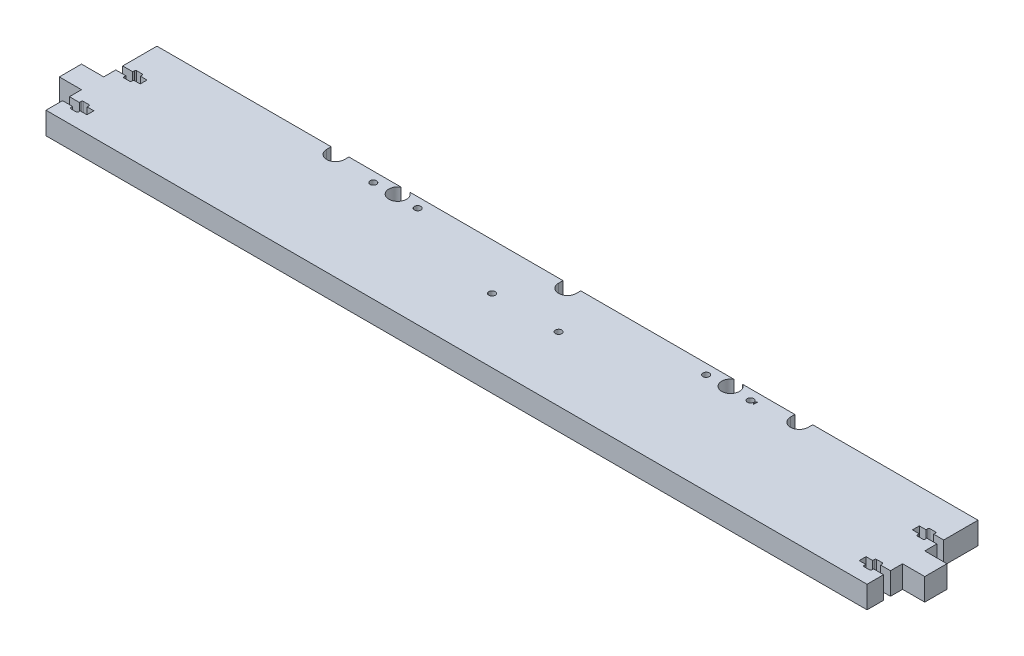
SolidWorks part; units mm, degrees
ref_plane "Front Plane" through (0, 0, 0) normal (0, 0, 1) x (1, 0, 0)
ref_plane "Top Plane" through (0, 0, 0) normal (0, 1, 0) x (1, 0, 0)
ref_plane "Right Plane" through (0, 0, 0) normal (1, 0, 0) x (0, 0, -1)
sketch "Sketch1" plane through (0, 0, 0) normal (0, 1, 0) x (1, 0, 0)
  line L0 (0, 25) -> (0, -25)
  line L1 (-185, 25) -> (0, 25)
  line L2 (-185, 25) -> (-185, -25) construction
  line L3 (-185, -25) -> (0, -25)
  line L4 (-185, -4) -> (-195, -4) construction
  line L5 (-185, 25) -> (0, 0) construction
  line L6 (-185, -25) -> (0, 0) construction
  line L7 (-185, -9) -> (-195, -9)
  line L8 (-195, -9) -> (-195, 1)
  line L9 (-195, 1) -> (-185, 1)
  line L10 (-185, 1) -> (-185, 25)
  line L11 (-185, -9) -> (-185, -25)
  line L47 (0, -25) -> (0, 25) construction
  line L89 (0, -25) -> (0, 25) construction
  point P0 (0, 0)
  dimension "D1" = 185
  dimension "D25" = 25
  dimension "D4" = 50
  dimension "D3" = 21
  dimension "D5" = 10
  dimension "D6" = 10
  dimension "D7" = 5
extrude "MainBody" add sketch "Sketch1" along normal blind 10 contours L3 region at (-93.5428, 0, 0.0428)
sketch "Sketch5" plane through (0, 10, 0) normal (0, 1, 0) x (1, 0, 0)
  line L0 (-185, 8) -> (-174, 8) construction
  line L1 (-185, 1) -> (-185, 25) construction
  line L2 (-185, 9.55) -> (-174, 9.55) construction
  line L3 (-174, 9.55) -> (-174, 6.45) construction
  line L4 (-174, 6.45) -> (-185, 6.45) construction
  line L5 (-185, 9.55) -> (-180.5, 9.55)
  line L6 (-180.5, 9.55) -> (-180.5, 10.35)
  line L7 (-180, 10.85) -> (-177.5, 10.85)
  line L8 (-177, 10.35) -> (-177, 9.55)
  line L9 (-177, 9.55) -> (-174, 9.55)
  line L10 (-174, 9.55) -> (-174, 6.45)
  line L11 (-185, 6.45) -> (-185, 9.55)
  line L12 (-195, -9) -> (-195, 1) construction
  line L13 (-185, 6.45) -> (-174, 6.45) construction
  line L14 (-177, 6.45) -> (-174, 6.45)
  line L15 (-177, 5.65) -> (-177, 6.45)
  line L16 (-180, 5.15) -> (-177.5, 5.15)
  line L17 (-180.5, 6.45) -> (-180.5, 5.65)
  line L18 (-185, 6.45) -> (-180.5, 6.45)
  line L19 (-185, 1) -> (-185, -9) construction
  line L20 (-195, -4) -> (-185, -4) construction
  line L21 (-195, -9) -> (-195, 1) construction
  line L22 (-185, -14.45) -> (-174, -14.45) construction
  line L23 (-174, -14.45) -> (-185, -14.45) construction
  line L24 (-174, -17.55) -> (-174, -14.45) construction
  line L25 (-185, -17.55) -> (-174, -17.55) construction
  line L26 (-185, -16) -> (-174, -16) construction
  line L27 (-185, -14.45) -> (-180.5, -14.45)
  line L28 (-180.5, -14.45) -> (-180.5, -13.65)
  line L29 (-180, -13.15) -> (-177.5, -13.15)
  line L30 (-177, -13.65) -> (-177, -14.45)
  line L31 (-177, -14.45) -> (-174, -14.45)
  line L32 (-185, -14.45) -> (-185, -17.55)
  line L33 (-174, -17.55) -> (-174, -14.45)
  line L34 (-177, -17.55) -> (-174, -17.55)
  line L35 (-177, -18.35) -> (-177, -17.55)
  line L36 (-180, -18.85) -> (-177.5, -18.85)
  line L37 (-180.5, -17.55) -> (-180.5, -18.35)
  line L38 (-185, -17.55) -> (-180.5, -17.55)
  line L39 (-185, 6.45) -> (-174, 6.45) construction
  arc A0 (-177.5, 10.85) -> (-177, 10.35) centre (-177.5, 10.35) cw
  arc A1 (-180.5, 10.35) -> (-180, 10.85) centre (-180, 10.35) cw
  arc A2 (-180.5, 5.65) -> (-180, 5.15) centre (-180, 5.65) ccw
  arc A3 (-177.5, 5.15) -> (-177, 5.65) centre (-177.5, 5.65) ccw
  arc A4 (-177.5, -13.15) -> (-177, -13.65) centre (-177.5, -13.65) cw
  arc A5 (-180.5, -13.65) -> (-180, -13.15) centre (-180, -13.65) cw
  arc A6 (-180.5, -18.35) -> (-180, -18.85) centre (-180, -18.35) ccw
  arc A7 (-177.5, -18.85) -> (-177, -18.35) centre (-177.5, -18.35) ccw
  point P6 (-195, -4)
  point P17 (-177, 10.85)
  point P20 (-180.5, 10.85)
  point P29 (-180.5, 5.15)
  point P30 (-177, 5.15)
  point P61 (-177, -13.15)
  point P62 (-180.5, -13.15)
  point P63 (-180.5, -18.85)
  point P64 (-177, -18.85)
  dimension "D8" = 0.5
  dimension "D1" = 11
  dimension "D2" = 1.55
  dimension "D4" = 3.5
  dimension "D5" = 8
  dimension "D6" = 2.85
  dimension "D7" = 12
extrude "ScrewCutouts" cut sketch "Sketch5" against normal through all
mirror "Mirror1" about plane through (0, 0, 0) normal (1, 0, 0) of "ScrewCutouts", "MainBody"
sketch "Sketch3" plane through (0, 10, 0) normal (0, 1, 0) x (1, 0, 0)
  line L0 (2, 25) -> (2, -25) construction
  line L1 (-185, 25) -> (185, 25) construction
  line L2 (-185, -25) -> (185, -25) construction
  line L3 (-63, 20.5) -> (-83, 20.5) construction
  line L4 (-73, 17.5) -> (-73, 25.5) construction
  line L5 (77, 17.5) -> (77, 25.5) construction
  line L6 (67, 20.5) -> (87, 20.5) construction
  circle A0 centre (-73, 21.5) radius 4
  circle A1 centre (-83, 20.5) radius 1.45
  circle A2 centre (-63, 20.5) radius 1.45
  circle A3 centre (67, 20.5) radius 1.45
  circle A4 centre (87, 20.5) radius 1.45
  circle A5 centre (77, 21.5) radius 4
  dimension "D2" = 8
  dimension "D4" = 2.9
  dimension "D1" = 3.5
  dimension "D5" = 75
  dimension "D6" = 2
  dimension "D3" = 10
  dimension "D7" = 1
extrude "RodCutouts" cut sketch "Sketch3" against normal through all
sketch "Sketch6" plane through (0, 10, 0) normal (0, 1, 0) x (1, 0, 0)
  line L0 (-73, 21.5) -> (77, 21.5) construction
  line L1 (2, 21.5) -> (2, -25) construction
  line L2 (-185, -25) -> (185, -25) construction
  line L3 (17, 4) -> (-13, 4) construction
  line L4 (-71.0635, 25) -> (75.0635, 25) construction
  circle A0 centre (-13, 4) radius 1.45
  circle A1 centre (17, 4) radius 1.45
  point P13 (2, 4)
  dimension "D3" = 21
  dimension "D1" = 2.9
  dimension "D2" = 15
extrude "Cut-Extrude1" cut sketch "Sketch6" against normal through all
sketch "Sketch7" plane through (0, 10, 0) normal (0, 1, 0) x (1, 0, 0)
  line L0 (-73, 21.5) -> (77, 21.5) construction
  line L1 (2, 21.5) -> (2, -25) construction
  line L3 (-102.5, 25) -> (-102.5, 23) construction
  line L4 (-185, 25) -> (-74.9365, 25) construction
  line L5 (-98.5, 25) -> (-98.5, 23)
  line L6 (-106.5, 25) -> (-106.5, 23)
  line L7 (106.5, 25) -> (106.5, 23) construction
  line L8 (102.5, 25) -> (102.5, 23)
  line L9 (110.5, 25) -> (110.5, 23)
  line L12 (-185, -25) -> (185, -25) construction
  arc A0 (-98.5, 25) -> (-106.5, 25) centre (-102.5, 25) ccw
  arc A1 (-106.5, 23) -> (-98.5, 23) centre (-102.5, 23) ccw
  arc A2 (102.5, 25) -> (110.5, 25) centre (106.5, 25) cw
  arc A3 (110.5, 23) -> (102.5, 23) centre (106.5, 23) cw
  point P12 (-102.5, 24)
  point P19 (106.5, 24)
  dimension "D1" = 4
  dimension "D2" = 2
  dimension "D3" = 104.5
extrude "BedAdjustmentScrewCutout" cut sketch "Sketch7" against normal through all
sketch "Sketch8" plane through (0, 10, 0) normal (0, 1, 0) x (1, 0, 0)
  line L0 (88.25, 20.5) -> (89.25, 20.5) construction
  line L1 (88.45, 20.5) -> (88.45, 25) construction
  line L2 (88.25, 20.5) -> (89.25, 21.5)
  line L3 (89.25, 21.5) -> (89.25, 19.5)
  line L4 (88.25, 20.5) -> (89.25, 19.5)
  line L5 (78.9365, 25) -> (102.5, 25) construction
  circle A1 centre (87, 20.5) radius 1.45 construction
  point P9 (89.25, 20.5)
  dimension "D1" = 1
  dimension "D2" = 1
  dimension "D3" = 0.2
extrude "DirectionKey" cut sketch "Sketch8" against normal through all
sketch "Sketch9" plane through (0, 10, 0) normal (0, 1, 0) x (1, 0, 0)
  line L0 (-13, 4) -> (17, 4) construction
  line L1 (2, 4) -> (2, 25) construction
  line L2 (-71.0635, 25) -> (75.0635, 25) construction
  line L3 (2, 27) -> (2, 23) construction
  line L4 (6, 27) -> (6, 23)
  line L5 (-2, 27) -> (-2, 23)
  arc A0 (6, 27) -> (-2, 27) centre (2, 27) ccw
  arc A1 (-2, 23) -> (6, 23) centre (2, 23) ccw
  point P10 (2, 25)
  dimension "D1" = 4
  dimension "D2" = 2
extrude "Cut-Extrude2" cut sketch "Sketch9" against normal through all
equation "\"Y-ROD-SPACING\"=75"
equation "\"Y-BED-OFFSET\"=2"
equation "\"T-SLOT-NUT-FILLET-RADIUS\"=0.5"
equation "\"T-SLOT-SCREW-SHAFT-RADIUS\"=1.55"
equation "\"T-SLOT-SCREW-SHAFT-CUTOUT-LENGTH\"=11"
equation "\"T-SLOT-NUT-DEPTH\"=3.5"
equation "\"T-SLOT-NUT-WIDTH\"=2.85"
equation "\"T-SLOT-NUT-END-DISTANCE\"=8"
equation "\"ACRYLIC-TAB-CUTOUT-SIZE\"=\"ACRYLIC-THICKNESS\"+\"ACRYLIC-TAB-TOLERANCE\"*2"
equation "\"ACRYLIC-M3-HOLE\"=2.9"
equation "\"D1@Sketch5\"=\"T-SLOT-SCREW-SHAFT-CUTOUT-LENGTH\""
equation "\"D2@Sketch5\"=\"T-SLOT-SCREW-SHAFT-RADIUS\""
equation "\"D4@Sketch5\"=\"T-SLOT-NUT-DEPTH\""
equation "\"D5@Sketch5\"=\"T-SLOT-NUT-END-DISTANCE\""
equation "\"D6@Sketch5\"=\"T-SLOT-NUT-WIDTH\""
equation "\"D8@Sketch5\"=\"T-SLOT-NUT-FILLET-RADIUS\""
equation "\"D4@Sketch3\"=\"ACRYLIC-M3-HOLE\""
equation "\"D5@Sketch3\"=\"Y-ROD-SPACING\""
equation "\"D6@Sketch3\"=\"Y-BED-OFFSET\""
equation "\"Y-BED-ROD-INSET\"=3.5"
equation "\"D1@Sketch3\"=\"Y-BED-ROD-INSET\""
equation "\"SMOOTHROD-CAP-SCREW-DISTANCE\"=20"
equation "\"D3@Sketch3\"=\"SMOOTHROD-CAP-SCREW-DISTANCE\"/2"
equation "\"ACRYLIC-TAB-WIDTH\"=\"ACRYLIC-THICKNESS\""
equation "\"FRAME-WIDTH-INNER\"=370"
equation "\"D6@Sketch1\"=\"ACRYLIC-TAB-WIDTH\""
equation "\"D5@Sketch1\"=\"ACRYLIC-TAB-WIDTH\""
equation "\"D1@Sketch1\"=\"FRAME-WIDTH-INNER\"/2"
equation "\"X-ROD-SPACING\"=45"
equation "\"Z-ROD-SPACING\"=17.5"
equation "\"ACRYLIC-THICKNESS\"=10"
equation "\"ACRYLIC-THICKNESS2\"=4.5"
equation "\"NEMA17-HOLE-SPACING\"=31"
equation "\"NEMA17-CENTRAL-CUTOUT\"=22.5"
equation "\"Z-BRACKET-REACH\"=55"
equation "\"TOP-BRACKET-SPACING\"=40"
equation "\"SMOOTHROD-X-LENGTH\"=350"
equation "\"SMOOTHROD-Y-LENGTH\"=350"
equation "\"SMOOTHROD-Z-LENGTH\"=350"
equation "\"SMOOTHROD-TIGHTENING-HEADROOM\"=.25"
equation "\"LEADSCREW-Z-LENGTH\"=300"
equation "\"SCREW-LENGTH-FRAME\"=\"ACRYLIC-THICKNESS\" + 10"
equation "\"SCREW-HEAD-RADIUS\"=6"
equation "\"PRINTED-X-SMOOTHROD-DIAMETER\"=9.0"
equation "\"PRINTED-X-SMOOTHROD-CUTOUT\"=10"
equation "\"PRINTED-X-BASE-HEIGHT\"=10"
equation "\"PRINTED-LM8UU-CUTOUT-SIZE\"=15.5"
equation "\"PRINTED-LM8UU-CUTOUT-LENGTH\"=24.5"
equation "\"PRINTED-X-IDLER-HEIGHT\"=16"
equation "\"PSU-MOUNTING-WIDTH\"=95"
equation "\"PSU-MOUNTING-HEIGHT\"=177"
equation "\"D1@MainBody\"=\"ACRYLIC-THICKNESS\""
equation "\"D7@Sketch1\"=\"ACRYLIC-TAB-WIDTH\"/2"
equation "\"D1@Sketch6\"=\"ACRYLIC-M3-HOLE\""
equation "\"Y-BELT-TO-ROD-DISTANCE\"=20"
equation "\"Y-BED-SCREW-SPACING\"=209"
equation "\"Z-ROD-INSET\"=13.5"
equation "\"SPOOL-HOLDER-ROD-SPACING\"=150"
equation "\"D3@Sketch7\"=\"Y-BED-SCREW-SPACING\"/2"
equation "\"Y-BED-SCREW-CUTOUT-SLOT-HEIGHT\"=2"
equation "\"D2@Sketch7\"=\"Y-BED-SCREW-CUTOUT-SLOT-HEIGHT\""
equation "\"ACRYLIC-TAB-TOLERANCE\"=-.05"
equation "\"SCREW-LENGTH-MOTOR\"=\"ACRYLIC-THICKNESS\" + 5"
equation "\"SCREW-LENGTH-EXTRUDER\"=28"
equation "\"PRINTED-M3-HOLE\"=3.5"
equation "\"ACRYLIC-X-CARRIAGE-WIDTH\"=55"
equation "\"ACRYLIC-X-CARRIAGE-HEIGHT\"=75"
equation "\"ACRYLIC-X-CARRIAGE-LM8UU-CUTOUT-WIDTH\"=24.25"
equation "\"ACRYLIC-X-CARRIAGE-LM8UU-CUTOUT-HEIGHT\"=11.0"
equation "\"ACRYLIC-X-CARRIAGE-SCREW-SPACING-X\"=15"
equation "\"ACRYLIC-X-CARRIAGE-SCREW-SPACING-Y\"=33"
equation "\"ACRYLIC-X-CARRIAGE-CENTER-TAB-SPACING\"=14"
equation "\"ACRYLIC-X-CARRIAGE-EXTRUDER-OFFSET\"=26"
equation "\"ACRYLIC-X-CARRIAGE-EXTRUDER-ANGLE\"=90"
equation "\"ACRYLIC-X-CARRIAGE-EXTRUDER-SHELF-DEPTH\"=\"ACRYLIC-X-CARRIAGE-EXTRUDER-OFFSET\" + 28"
equation "\"ACRYLIC-X-CARRIAGE-EXTRUDER-BRACE-SPACING\"=23"
equation "\"ACRYLIC-X-CARRIAGE-EXTRUDER-BRACE-TAB-OFFSET\"=20"
equation "\"ACRYLIC-X-CARRIAGE-EXTRUDER-BRACE-HEIGHT\"=35"
equation "\"ACRYLIC-X-CARRIAGE-EXTRUDER-BRACE-SCREW-SPACING\"=22"
equation "\"ACRYLIC-X-CARRIAGE-DUAL-WIDTH-MULTIPLIER\"=1.65"
equation "\"ACRYLIC-X-CARRIAGE-DUAL-HOTEND-SPACING\"=42"
equation "\"ACRYLIC-X-CARRIAGE-DUAL-WIDTH\"=75"
equation "\"ACRYLIC-X-CARRIAGE-DUAL-HOTEND-SEPARATION\"=36"
equation "\"ACRYLIC-X-CARRIAGE-DUAL-MOUNT-PLATE-DEPTH\"=75"
equation "\"ACRYLIC-X-CARRIAGE-DUAL-MOUNT-BRACE-WIDTH\"=33"
equation "\"ACRYLIC-X-CARRIAGE-DUAL-MOUNT-SCREW-WIDTH\"=40"
equation "\"BLOWER-FAN-WIDTH\"=15"
equation "\"D2@Sketch9\"=\"Y-BED-SCREW-CUTOUT-SLOT-HEIGHT\""
